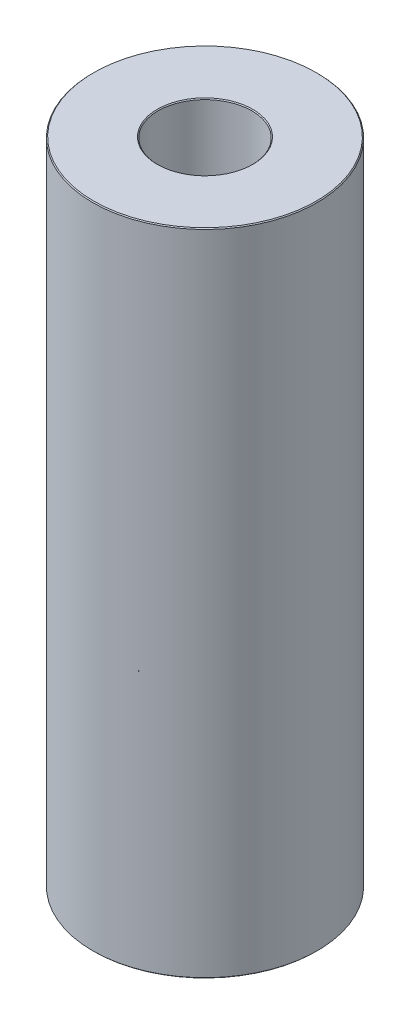
SolidWorks part; units mm, degrees
ref_plane "Front Plane" through (0, 0, 0) normal (0, 0, 1) x (1, 0, 0)
ref_plane "Top Plane" through (0, 0, 0) normal (0, 1, 0) x (1, 0, 0)
ref_plane "Right Plane" through (0, 0, 0) normal (1, 0, 0) x (0, 0, -1)
sketch "Sketch1" plane through (0, 0, 0) normal (0, 1, 0) x (1, 0, 0)
  circle A0 centre (0, 0) radius 57.5
  dimension "SLEEVE_OD" = 115
extrude "Boss-Extrude1" add sketch "Sketch1" along normal blind 333.0269
sketch "Sketch2" plane through (0, 0, 0) normal (0, 1, 0) x (1, 0, 0)
  circle A0 centre (0, 0) radius 24.0242
  dimension "BORE_D" = 48.0484
extrude "Cut-Extrude1" cut sketch "Sketch2" along normal through all
chamfer "Chamfer1" distance 0.4542 angle 45 4 edges at (0, 333.0269, 24.0242) (0, 0, 24.0242) (0, 0, 57.5) (0, 333.0269, 57.5)
